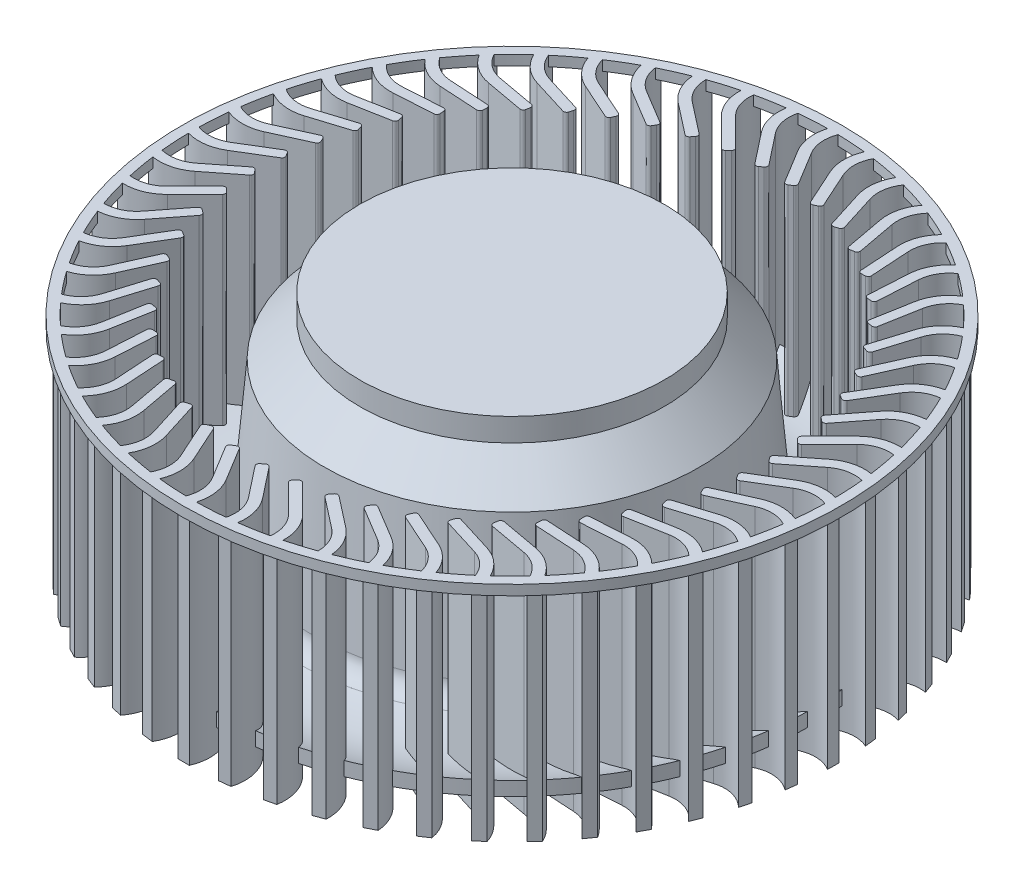
SolidWorks part; units mm, degrees
material "POM - C (Noir)"
ref_plane "Plan de face" through (0, 0, 0) normal (0, 0, 1) x (1, 0, 0)
ref_plane "Plan de dessus" through (0, 0, 0) normal (0, 1, 0) x (1, 0, 0)
ref_plane "Plan de droite" through (0, 0, 0) normal (1, 0, 0) x (0, 0, -1)
sketch "Esquisse1" plane through (0, 0, 0) normal (0, 0, 1) x (1, 0, 0)
  line L2 (-15.2, -2.3) -> (-18.7, -5.8)
  line L3 (-18.7, -5.8) -> (-19.8905, -19.7196)
  line L4 (-20, -21) -> (-30, -21) construction
  line L5 (0, 0) -> (0, -21) construction
  line L6 (-25, -21) -> (-25, -9) construction
  line L7 (-17.4452, -6.3836) -> (-18.5952, -19.8304)
  line L8 (-14.5097, -3.4482) -> (-17.4452, -6.3836)
  line L9 (-30, -21) -> (-30, -22.3974)
  line L10 (0, 0) -> (0, -1.3)
  line L11 (0, 0) -> (-15.2, 0)
  line L12 (-15.2, 0) -> (-15.2, -2.3)
  arc A4 (-30, -21) -> (-21.3165, -21.4672) centre (-25, -9) ccw
  arc A5 (-19.8905, -19.7196) -> (-21.3165, -21.4672) centre (-21.8832, -19.5492) cw
  arc A6 (-30, -22.3974) -> (-20.9482, -22.714) centre (-25, -9) ccw
  arc A7 (-18.5952, -19.8304) -> (-20.9482, -22.714) centre (-21.8832, -19.5492) cw
  arc A8 (-10.563, -2.4268) -> (-14.5097, -3.4482) centre (0, -51.3761) ccw
  arc A9 (-10.563, -2.4268) -> (-8.9282, -2.1023) centre (-10, -0.9826) ccw
  arc A10 (0, -1.3) -> (-8.9282, -2.1023) centre (0, -51.3761) ccw
  arc A11 (-30.5, -22.2) -> (-20.9482, -22.714) centre (-25, -9) ccw construction
  arc A12 (-10.2451, -1.0319) -> (-15.2, -2.3) centre (0, -51.3761) ccw construction
  arc A13 (0, 0) -> (-9.7547, -0.9345) centre (0, -51.3761) ccw construction
  arc A14 (-10.2451, -1.0319) -> (-9.7547, -0.9345) centre (-10, -0.9826) ccw construction
  point P1 (-10, -0.9826)
  dimension "D10" = 13
  dimension "D11" = 2
  dimension "D1" = 30.4
  dimension "D2" = 37.4
  dimension "D3" = 40
  dimension "D4" = 60
  dimension "D5" = 2.3
  dimension "D6" = 45
  dimension "D7" = 21
  dimension "D12" = 1.3
revolve "Révolution1" add sketch "Esquisse1" angle 360 about L5
ref_plane "Plan2" through (0, -2, 0) normal (0, 1, 0) x (1, 0, 0)
sketch "Esquisse5" plane through (0, -2, 0) normal (0, 1, 0) x (1, 0, 0)
  line L0 (0, 0) -> (0, 32.425) construction
  line L1 (0, 32.2859) -> (-3, 32.2859) construction
  line L2 (-0.1856, 25.8357) -> (-2.5882, 28.887)
  line L3 (-0.9713, 25.2171) -> (-3.3739, 28.2684)
  line L4 (-3, 32.2859) -> (-4.1119, 32.1632)
  line L5 (-0.2357, 25.4144) -> (-0.55, 25.167)
  line L6 (0, 25.6) -> (-2.5882, 28.887) construction
  line L7 (-0.7857, 24.9814) -> (-3.3739, 28.2684) construction
  circle A0 centre (0, 0) radius 32.425 construction
  circle A1 centre (0, 0) radius 25.6 construction
  arc A2 (-3, 32.2859) -> (-2.5882, 28.887) centre (0, 30.925) ccw
  arc A3 (-4.1119, 32.1632) -> (-3.3739, 28.2684) centre (0, 30.925) ccw
  arc A4 (-3.9107, 32.699) -> (-3.3739, 28.2684) centre (0, 30.925) ccw construction
  arc A5 (-0.1856, 25.8357) -> (-0.2357, 25.4144) centre (-0.4213, 25.6501) cw
  arc A6 (-0.9713, 25.2171) -> (-0.55, 25.167) centre (-0.7356, 25.4027) ccw
  point P18 (0, 25.6)
  dimension "D1" = 64.85
  dimension "D2" = 51.2
  dimension "D4" = 1.5
  dimension "D6" = 0.3
  dimension "D3" = 3
  dimension "D5" = 1
extrude "Boss.-Extru.1" add sketch "Esquisse5" against normal blind 22.6
pattern_circular "Répétition circulaire2" count 52 over 360 about axis through (0, 0, 0) along (0, 1, 0) of "Boss.-Extru.1" reverse direction yes
sketch "Esquisse6" plane through (0, -2, 0) normal (0, 1, 0) x (1, 0, 0)
  circle A0 centre (0, 0) radius 32.9
  circle A1 centre (0, 0) radius 31.9
  dimension "D1" = 65.8
  dimension "D2" = 1
extrude "Boss.-Extru.2" add sketch "Esquisse6" against normal blind 1
sketch "草图1" plane through (0, 0, 0) normal (0, 1, 0) x (1, 0, 0)
  text T0 "R" font "Earth Orbiter Laser" height 10
extrude "凸台-拉伸1" [suppressed] add sketch "草图1" along normal blind 0.1
